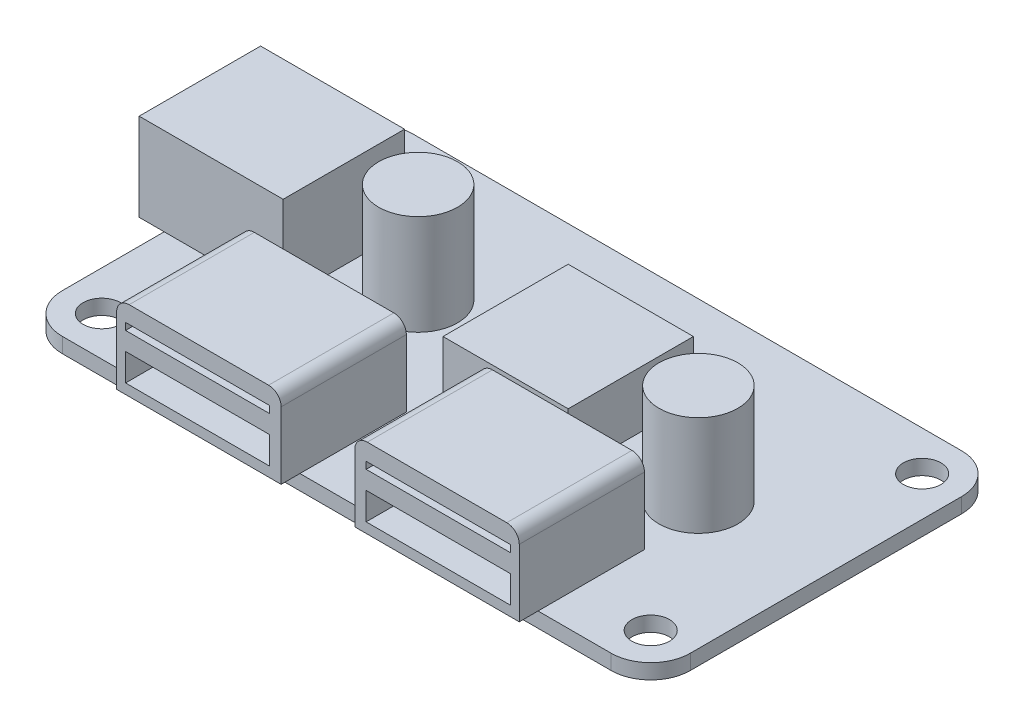
SolidWorks part; units mm, degrees
ref_plane "前视基准面" through (0, 0, 0) normal (0, 0, 1) x (1, 0, 0)
ref_plane "上视基准面" through (0, 0, 0) normal (0, 1, 0) x (1, 0, 0)
ref_plane "右视基准面" through (0, 0, 0) normal (1, 0, 0) x (0, 0, -1)
sketch "草图1" plane through (0, 0, 0) normal (0, 1, 0) x (1, 0, 0)
  line L0 (-32.5014, 0) -> (38.8338, 0) construction
  line L1 (-21.92, 14) -> (21.92, 14)
  line L2 (-25.08, 10.84) -> (-25.08, -10.84)
  line L3 (-21.92, -14) -> (21.92, -14)
  line L4 (25.08, 10.84) -> (25.08, -10.84)
  line L5 (0, 24.4523) -> (0, -28.5722) construction
  circle A0 centre (-21.92, 10.84) radius 1.5
  circle A1 centre (21.92, 10.84) radius 1.5
  circle A2 centre (21.92, -10.84) radius 1.5
  circle A3 centre (-21.92, -10.84) radius 1.5
  arc A4 (21.92, 14) -> (25.08, 10.84) centre (21.92, 10.84) cw
  arc A5 (21.92, -14) -> (25.08, -10.84) centre (21.92, -10.84) ccw
  arc A6 (-25.08, -10.84) -> (-21.92, -14) centre (-21.92, -10.84) ccw
  arc A7 (-21.92, 14) -> (-25.08, 10.84) centre (-21.92, 10.84) ccw
  point P0 (0, 0)
  point P20 (25.08, 14)
  point P23 (25.08, -14)
  point P26 (-25.08, -14)
  dimension "D3" = 3.16
  dimension "D4" = 3.16
  dimension "D5" = 3.16
  dimension "D1" = 28
  dimension "D2" = 50.16
extrude "凸台-拉伸1" add sketch "草图1" along normal blind 1.2
sketch "草图2" plane through (0, 1.2, 0) normal (0, 1, 0) x (1, 0, 0)
  line L0 (0, 18.4099) -> (0, -19.8075) construction
  line L1 (-27.08, 7) -> (-15.58, 7)
  line L2 (-27.08, 7) -> (-27.08, -2.7)
  line L3 (-27.08, -2.7) -> (-15.58, -2.7)
  line L4 (-15.58, 7) -> (-15.58, -2.7)
  line L5 (-16.08, -15.5) -> (-2.94, -15.5)
  line L6 (-16.08, -15.5) -> (-16.08, -5.5)
  line L7 (-16.08, -5.5) -> (-2.94, -5.5)
  line L8 (-2.94, -15.5) -> (-2.94, -5.5)
  line L9 (21.92, 14) -> (-21.92, 14) construction
  line L10 (-25.08, 10.84) -> (-25.08, -10.84) construction
  line L12 (-21.92, -14) -> (21.92, -14) construction
  line L13 (2.94, -15.5) -> (2.94, -5.5)
  line L14 (16.08, -5.5) -> (2.94, -5.5)
  line L15 (16.08, -15.5) -> (16.08, -5.5)
  line L16 (16.08, -15.5) -> (2.94, -15.5)
  line L18 (-2.2038, 6.6921) -> (7.7962, 6.6921)
  line L19 (-2.2038, 6.6921) -> (-2.2038, -3.3079)
  line L20 (-2.2038, -3.3079) -> (7.7962, -3.3079)
  line L21 (7.7962, 6.6921) -> (7.7962, -3.3079)
  circle A0 centre (-10.2128, 2.7145) radius 3.15
  circle A1 centre (14.8892, 0) radius 3.15
  point P29 (15.0505, 0)
  point P30 (0, 0)
  point P31 (16.08, 0)
  point P32 (0, 0)
  point P33 (14.8892, 0)
  point P34 (-10.2128, 2.7145)
  line M21 (-21.92, -14) -> (21.92, -14)
  dimension "D9" = 6.3
  dimension "D10" = 6.3
  dimension "D1" = 11.5
  dimension "D2" = 9.7
  dimension "D3" = 7
  dimension "D4" = 2
  dimension "D5" = 13.14
  dimension "D6" = 10
  dimension "D7" = 1.5
  dimension "D8" = 9
  dimension "D11" = 10
  dimension "D12" = 10
extrude "凸台-拉伸3" add sketch "草图2" along normal blind 6.36 separate body contours L8 L7 L6 M21 | L15 L14 L13 M21 | L5 L8 L6 M21 | L16 L15 L13 M21 region at (-9.51, 1.2, 14.75) region at (9.51, 1.2, 9.75) region at (9.51, 1.2, 14.75) region at (-9.51, 1.2, 9.75)
extrude "凸台-拉伸4" add sketch "草图2<4>" along normal blind 7 contours L1 L4 L3 L2
sketch "草图2<4>" plane through (0, 1.2, 0) normal (0, 1, 0) x (1, 0, 0) same geometry as "草图2"
extrude "凸台-拉伸5" add sketch "草图2<5>" along normal blind 8 contours A0 | A1
sketch "草图2<5>" plane through (0, 1.2, 0) normal (0, 1, 0) x (1, 0, 0) same geometry as "草图2"
extrude "凸台-拉伸6" add sketch "草图2<6>" along normal blind 4.5 contours L18 L21 L20 L19
sketch "草图2<6>" plane through (0, 1.2, 0) normal (0, 1, 0) x (1, 0, 0) same geometry as "草图2"
sketch "草图3" plane through (-27.08, 0, 0) normal (-1, 0, 0) x (0, 0, 1)
  line L0 (2.7, 8.2) -> (2.7, 1.2) construction
  circle A0 centre (-0.8, 4.7) radius 3
  circle A1 centre (-0.8, 4.7) radius 0.5
  dimension "D1" = 3.5
extrude "切除-拉伸2" cut sketch "草图3" against normal blind 9.2 contours A0 | A1
fillet "圆角1" radius 1 2 edges at (-2.94, 7.56, 10.5) (-16.08, 7.56, 10.5)
fillet "圆角2" radius 1 2 edges at (16.08, 7.56, 10.5) (2.94, 7.56, 10.5)
sketch "草图4" plane through (0, 0, 15.5) normal (0, 0, 1) x (1, 0, 0)
  line L0 (0, 13.4034) -> (0, -9.1781) construction
  line L1 (-15.365, 4.1808) -> (-3.8506, 4.1808)
  line L2 (-15.365, 4.1808) -> (-15.365, 2.0009)
  line L3 (-15.365, 2.0009) -> (-3.8506, 2.0009)
  line L4 (-3.8506, 4.1808) -> (-3.8506, 2.0009)
  line L5 (-15.365, 6.193) -> (-3.8506, 6.193)
  line L6 (-15.365, 6.193) -> (-15.365, 5.6341)
  line L7 (-15.365, 5.6341) -> (-3.8506, 5.6341)
  line L8 (-3.8506, 6.193) -> (-3.8506, 5.6341)
  line L9 (3.8506, 6.193) -> (3.8506, 5.6341)
  line L10 (15.365, 5.6341) -> (3.8506, 5.6341)
  line L11 (15.365, 6.193) -> (15.365, 5.6341)
  line L12 (15.365, 6.193) -> (3.8506, 6.193)
  line L13 (3.8506, 4.1808) -> (3.8506, 2.0009)
  line L14 (15.365, 2.0009) -> (3.8506, 2.0009)
  line L15 (15.365, 4.1808) -> (15.365, 2.0009)
  line L16 (15.365, 4.1808) -> (3.8506, 4.1808)
extrude "切除-拉伸3" cut sketch "草图4" against normal blind 7.2
